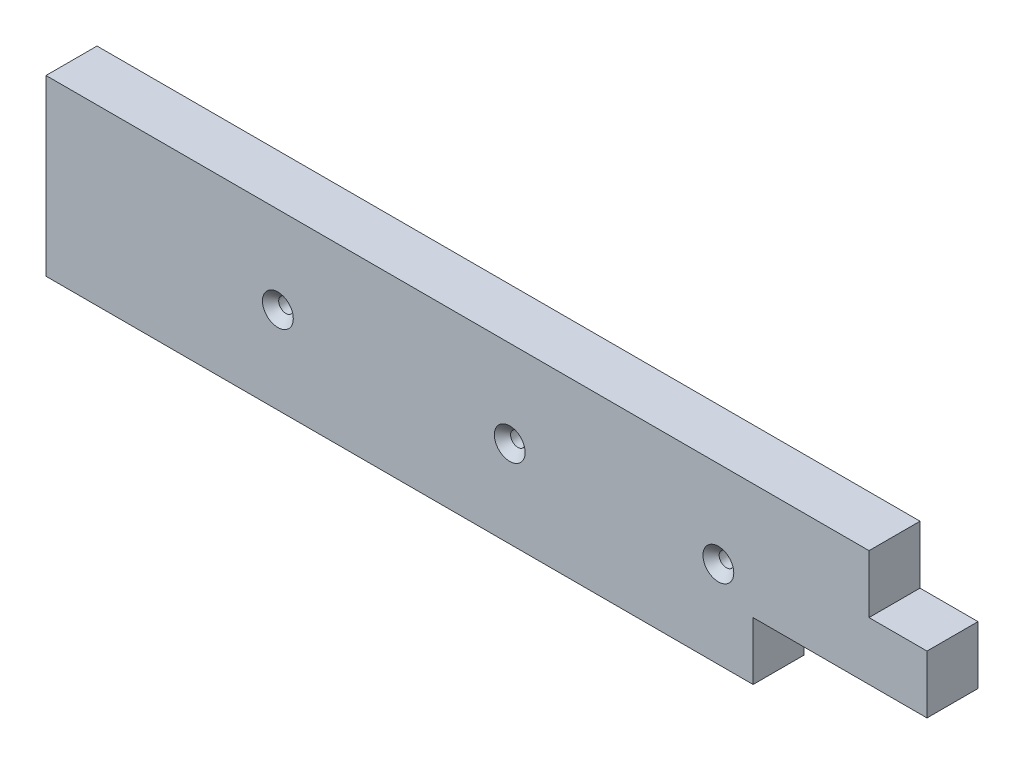
SolidWorks part; units mm, degrees
ref_plane "Front Plane" through (0, 0, 0) normal (0, 0, 1) x (1, 0, 0)
ref_plane "Top Plane" through (0, 0, 0) normal (0, 1, 0) x (1, 0, 0)
ref_plane "Right Plane" through (0, 0, 0) normal (1, 0, 0) x (0, 0, -1)
sketch "Sketch1" plane through (0, 0, 0) normal (0, 1, 0) x (1, 0, 0)
  line L1 (-193.0064, -11.176) -> (193.0064, -11.176)
  line L2 (-193.0064, -11.176) -> (-193.0064, 11.176)
  line L3 (-193.0064, 11.176) -> (193.0064, 11.176)
  line L4 (193.0064, -11.176) -> (193.0064, 11.176)
  line L5 (-193.0064, -11.176) -> (193.0064, 11.176) construction
  line L6 (-193.0064, 11.176) -> (193.0064, -11.176) construction
  point P0 (0, 0)
extrude "Boss-Extrude1" add sketch "Sketch1" along normal mid plane 76.2 contours L1 L4 L3 L2
sketch "Sketch3" plane through (0, 0, 11.176) normal (0, 0, 1) x (1, 0, 0)
  line L1 (167.6064, 12.7) -> (193.0064, 12.7)
  line L2 (193.0064, 38.1) -> (193.0064, 12.7)
  line L3 (167.6064, 12.7) -> (167.6064, 38.1)
  line L4 (167.6064, 38.1) -> (193.0064, 38.1)
  line L5 (116.8199, -12.7) -> (193.0064, -12.7)
  line L6 (116.8199, -12.7) -> (116.8199, -38.1)
  line L7 (116.8199, -38.1) -> (193.0064, -38.1)
  line L8 (193.0064, -12.7) -> (193.0064, -38.1)
hole_wizard "CSK for M6 Hex Socket Countersunk Head Screw6" positions "Sketch21" profile "Sketch20" countersink size "M6" standard "Lanco STD" end condition through all
sketch "Sketch21" plane through (0, 0, 11.176) normal (0, 0, 1) x (1, 0, 0)
  line L0 (-193.0064, 38.1) -> (-193.0064, -38.1) construction
  point P0 (-91.4064, 0)
  point P3 (-193.0064, 0)
  dimension "D1" = 101.6
sketch "Sketch20" plane through (-91.4064, 0, 11.176) normal (1, 0, 0) x (0, -1, 0)
  line L0 (0, 0) -> (0, 22.352)
  line L1 (0, 22.352) -> (3.2, 22.352)
  line L2 (3.2, 22.352) -> (3.2, 3.55)
  line L3 (3.2, 3.55) -> (6.75, 0)
  line L5 (6.75, 0) -> (0, 0)
  line L6 (-3.2, 3.55) -> (-6.75, 0) construction
  line L11 (0, -6.35) -> (0, 107.95) construction
  dimension "Thru Hole Dia." = 6.4
  dimension "Thru Hole Depth" = 22.352
  dimension "Near C'Sink Dia." = 13.5
  dimension "Near C'Sink Angle" = 90
hole_wizard "CSK for M6 Hex Socket Countersunk Head Screw7" positions "Sketch23" profile "Sketch22" countersink size "M6" standard "Lanco STD" end condition through all
sketch "Sketch23" plane through (0, 0, 11.176) normal (0, 0, 1) x (1, 0, 0)
  line L1 (-193.0064, 38.1) -> (-193.0064, -38.1) construction
  point P0 (10.1936, 0)
  point P5 (-193.0064, 0)
  dimension "D1" = 203.2
sketch "Sketch22" plane through (10.1936, 0, 11.176) normal (1, 0, 0) x (0, -1, 0)
  line L0 (0, 0) -> (0, 22.352)
  line L1 (0, 22.352) -> (3.2, 22.352)
  line L2 (3.2, 22.352) -> (3.2, 3.55)
  line L3 (3.2, 3.55) -> (6.75, 0)
  line L5 (6.75, 0) -> (0, 0)
  line L6 (-3.2, 3.55) -> (-6.75, 0) construction
  line L11 (0, -6.35) -> (0, 107.95) construction
  dimension "Thru Hole Dia." = 6.4
  dimension "Thru Hole Depth" = 22.352
  dimension "Near C'Sink Dia." = 13.5
  dimension "Near C'Sink Angle" = 90
hole_wizard "CSK for M6 Hex Socket Countersunk Head Screw8" positions "Sketch25" profile "Sketch24" countersink size "M6" standard "Lanco STD" end condition through all
sketch "Sketch25" plane through (0, 0, 11.176) normal (0, 0, 1) x (1, 0, 0)
  point P0 (101.6, 0)
  dimension "D1" = 101.6
sketch "Sketch24" plane through (101.6, 0, 11.176) normal (1, 0, 0) x (0, -1, 0)
  line L0 (0, 0) -> (0, 22.352)
  line L1 (0, 22.352) -> (3.2, 22.352)
  line L2 (3.2, 22.352) -> (3.2, 3.55)
  line L3 (3.2, 3.55) -> (6.75, 0)
  line L5 (6.75, 0) -> (0, 0)
  line L6 (-3.2, 3.55) -> (-6.75, 0) construction
  line L11 (0, -6.35) -> (0, 107.95) construction
  dimension "Thru Hole Dia." = 6.4
  dimension "Thru Hole Depth" = 22.352
  dimension "Near C'Sink Dia." = 13.5
  dimension "Near C'Sink Angle" = 90
extrude "Cut-Extrude1" cut sketch "Sketch3" against normal through all
